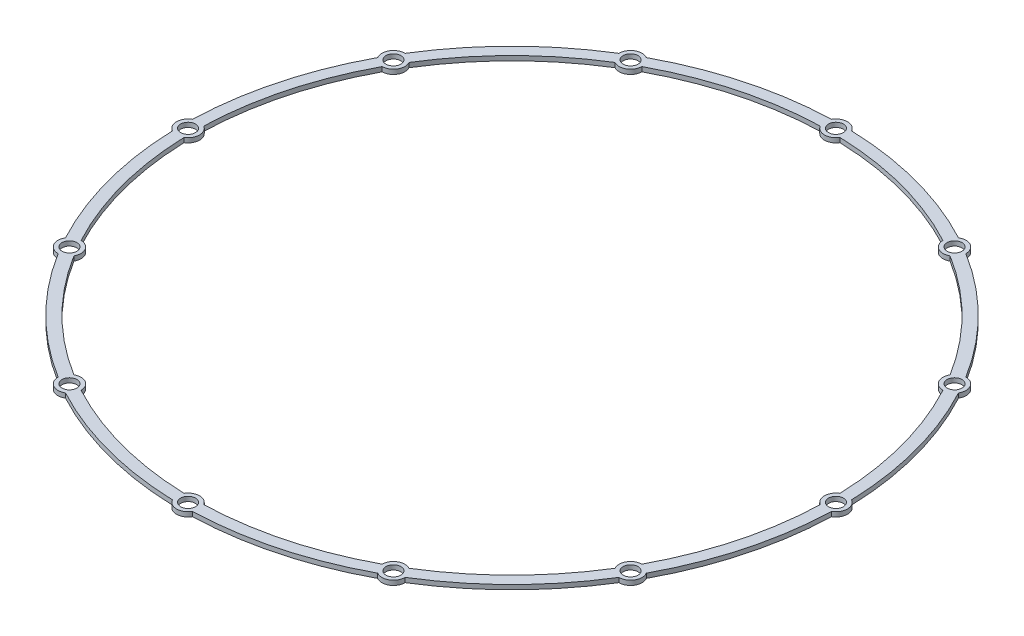
SolidWorks part; units mm, degrees
material "6061 Alloy"
ref_plane "Front Plane" through (0, 0, 0) normal (0, 0, 1) x (1, 0, 0)
ref_plane "Top Plane" through (0, 0, 0) normal (0, 1, 0) x (1, 0, 0)
ref_plane "Right Plane" through (0, 0, 0) normal (1, 0, 0) x (0, 0, -1)
sketch "Sketch1" plane through (0, 0, 0) normal (0, 1, 0) x (1, 0, 0)
  circle A0 centre (0, 0) radius 71.755 construction
  circle A1 centre (0, 0) radius 73.025
  circle A2 centre (0, 0) radius 70.485
  circle A3 centre (0, 0) radius 74.295
  circle A4 centre (0, 0) radius 69.215
  circle A5 centre (0, -71.755) radius 1.651
  circle A6 centre (0, -71.755) radius 2.54
  dimension "D1" = 143.51
  dimension "D6" = 3.302
  dimension "D2" = 1.27
  dimension "D3" = 1.27
  dimension "D4" = 2.54
  dimension "D5" = 2.54
extrude "Boss-Extrude1" add sketch "Sketch1" along normal blind 1.016 contours A6 A1 A2 | A2 A6 A1 A5 | A1 A5 A2 | A1 A6 A2 A5 region at (50.9327, 0, 49.408) region at (-1.9394, 0, 71.7321) region at (1.9394, 0, 71.7321) region at (0, 0, 71.7531)
extrude "Boss-Extrude2" add sketch "Sketch1<3>" along normal blind 1.016 contours A2 A6 A5 | A6 A1 A5 region at (0, 0, 73.5973) region at (0, 0, 69.8977)
sketch "Sketch1<3>" plane through (0, 0, 0) normal (0, 1, 0) x (1, 0, 0) same geometry as "Sketch1"
extrude "Cut-Extrude1" cut sketch "Sketch1<4>" along normal up to surface (1.016 mm away) contours A1 A5 | A2 A5 | A1 A5 A2 region at (0, 0, 71.7531) region at (0, 0, 73.1775) region at (0, 0, 70.3295) up to face at (0, 1.016, 0.635)
sketch "Sketch1<4>" plane through (0, 0, 0) normal (0, 1, 0) x (1, 0, 0) same geometry as "Sketch1"
pattern_circular "CirPattern2" count 12 over 360 about axis through (0, 1.016, 0) along (0, 1, 0) of "Cut-Extrude1", "Boss-Extrude2"
ref_plane "Plane1" through (0, 0.508, 0) normal (0, 1, 0) x (1, 0, 0)
sketch "Sketch2" plane through (0, 0.508, 0) normal (0, 1, 0) x (1, 0, 0)
  circle A0 centre (-62.1417, 35.8775) radius 1.651 construction
  circle A1 centre (-35.8775, 62.1417) radius 1.651 construction
  circle A2 centre (-71.755, 0) radius 1.651 construction
  circle A3 centre (-62.1417, -35.8775) radius 1.651 construction
  circle A4 centre (-35.8775, -62.1417) radius 1.651 construction
  circle A5 centre (0, -71.755) radius 1.651 construction
  circle A6 centre (35.8775, -62.1417) radius 1.651 construction
  circle A7 centre (62.1417, -35.8775) radius 1.651 construction
  circle A8 centre (71.755, 0) radius 1.651 construction
  circle A9 centre (62.1417, 35.8775) radius 1.651 construction
  circle A10 centre (35.8775, 62.1417) radius 1.651 construction
  circle A11 centre (0, 71.755) radius 1.651 construction
  circle A12 centre (-62.1417, 35.8775) radius 1.651
  circle A13 centre (-71.755, 0) radius 1.651
  circle A14 centre (-62.1417, -35.8775) radius 1.651
  circle A15 centre (-35.8775, -62.1417) radius 1.651
  circle A16 centre (0, -71.755) radius 1.651
  circle A17 centre (35.8775, -62.1417) radius 1.651
  circle A18 centre (62.1417, -35.8775) radius 1.651
  circle A19 centre (71.755, 0) radius 1.651
  circle A20 centre (62.1417, 35.8775) radius 1.651
  circle A21 centre (35.8775, 62.1417) radius 1.651
  circle A22 centre (0, 71.755) radius 1.651
  circle A23 centre (-35.8775, 62.1417) radius 1.651
  arc A24 (-38.4172, -62.1029) -> (-34.5741, -64.3217) centre (-35.8775, -62.1417) ccw
  arc A25 (-34.5741, -64.3217) -> (-2.2188, -72.9913) centre (0, 0) ccw
  arc A26 (-2.2188, -72.9913) -> (2.2188, -72.9913) centre (0, -71.755) ccw
  arc A27 (2.2188, -72.9913) -> (34.5741, -64.3217) centre (0, 0) ccw
  arc A28 (34.5741, -64.3217) -> (38.4172, -62.1029) centre (35.8775, -62.1417) ccw
  arc A29 (38.4172, -62.1029) -> (62.1029, -38.4172) centre (0, 0) ccw
  arc A30 (62.1029, -38.4172) -> (64.3217, -34.5741) centre (62.1417, -35.8775) ccw
  arc A31 (64.3217, -34.5741) -> (72.9913, -2.2188) centre (0, 0) ccw
  arc A32 (72.9913, -2.2188) -> (72.9913, 2.2188) centre (71.755, 0) ccw
  arc A33 (72.9913, 2.2188) -> (64.3217, 34.5741) centre (0, 0) ccw
  arc A34 (64.3217, 34.5741) -> (62.1029, 38.4172) centre (62.1417, 35.8775) ccw
  arc A35 (62.1029, 38.4172) -> (38.4172, 62.1029) centre (0, 0) ccw
  arc A36 (38.4172, 62.1029) -> (34.5741, 64.3217) centre (35.8775, 62.1417) ccw
  arc A37 (34.5741, 64.3217) -> (2.2188, 72.9913) centre (0, 0) ccw
  arc A38 (2.2188, 72.9913) -> (-2.2188, 72.9913) centre (0, 71.755) ccw
  arc A39 (-2.2188, 72.9913) -> (-34.5741, 64.3217) centre (0, 0) ccw
  arc A40 (-34.5741, 64.3217) -> (-38.4172, 62.1029) centre (-35.8775, 62.1417) ccw
  arc A41 (-38.4172, 62.1029) -> (-62.1029, 38.4172) centre (0, 0) ccw
  arc A42 (-62.1029, 38.4172) -> (-64.3217, 34.5741) centre (-62.1417, 35.8775) ccw
  arc A43 (-64.3217, 34.5741) -> (-72.9913, 2.2188) centre (0, 0) ccw
  arc A44 (-72.9913, 2.2188) -> (-72.9913, -2.2188) centre (-71.755, 0) ccw
  arc A45 (-72.9913, -2.2188) -> (-64.3217, -34.5741) centre (0, 0) ccw
  arc A46 (-64.3217, -34.5741) -> (-62.1029, -38.4172) centre (-62.1417, -35.8775) ccw
  arc A47 (-62.1029, -38.4172) -> (-38.4172, -62.1029) centre (0, 0) ccw
  arc A48 (-38.4172, -62.1029) -> (-34.5741, -64.3217) centre (-35.8775, -62.1417) ccw
  arc A49 (-34.5741, -64.3217) -> (-2.2188, -72.9913) centre (0, 0) ccw
  arc A50 (-2.2188, -72.9913) -> (2.2188, -72.9913) centre (0, -71.755) ccw
  arc A51 (2.2188, -72.9913) -> (34.5741, -64.3217) centre (0, 0) ccw
  arc A52 (34.5741, -64.3217) -> (38.4172, -62.1029) centre (35.8775, -62.1417) ccw
  arc A53 (38.4172, -62.1029) -> (62.1029, -38.4172) centre (0, 0) ccw
  arc A54 (62.1029, -38.4172) -> (64.3217, -34.5741) centre (62.1417, -35.8775) ccw
  arc A55 (64.3217, -34.5741) -> (72.9913, -2.2188) centre (0, 0) ccw
  arc A56 (72.9913, -2.2188) -> (72.9913, 2.2188) centre (71.755, 0) ccw
  arc A57 (72.9913, 2.2188) -> (64.3217, 34.5741) centre (0, 0) ccw
  arc A58 (64.3217, 34.5741) -> (62.1029, 38.4172) centre (62.1417, 35.8775) ccw
  arc A59 (62.1029, 38.4172) -> (38.4172, 62.1029) centre (0, 0) ccw
  arc A60 (38.4172, 62.1029) -> (34.5741, 64.3217) centre (35.8775, 62.1417) ccw
  arc A61 (34.5741, 64.3217) -> (2.2188, 72.9913) centre (0, 0) ccw
  arc A62 (2.2188, 72.9913) -> (-2.2188, 72.9913) centre (0, 71.755) ccw
  arc A63 (-2.2188, 72.9913) -> (-34.5741, 64.3217) centre (0, 0) ccw
  arc A64 (-34.5741, 64.3217) -> (-38.4172, 62.1029) centre (-35.8775, 62.1417) ccw
  arc A65 (-38.4172, 62.1029) -> (-62.1029, 38.4172) centre (0, 0) ccw
  arc A66 (-62.1029, 38.4172) -> (-64.3217, 34.5741) centre (-62.1417, 35.8775) ccw
  arc A67 (-64.3217, 34.5741) -> (-72.9913, 2.2188) centre (0, 0) ccw
  arc A68 (-72.9913, 2.2188) -> (-72.9913, -2.2188) centre (-71.755, 0) ccw
  arc A69 (-72.9913, -2.2188) -> (-64.3217, -34.5741) centre (0, 0) ccw
  arc A70 (-64.3217, -34.5741) -> (-62.1029, -38.4172) centre (-62.1417, -35.8775) ccw
  arc A71 (-62.1029, -38.4172) -> (-38.4172, -62.1029) centre (0, 0) ccw
  dimension "D1" = 0
equation "\"Middle Coupler Inner Daimeter\"= 4.75in"
equation "\"Middle Coupler  Wall Thickness\" = 0.25in"
equation "\"Middle Coupler Bottom Thickness\"= 0.2in"
equation "\"Bearing Rail Offset\"= 0.45in"
equation "\"3-56 UNF Tap\"= 0.089in"
equation "\"3-56 UNF Clearance\"= 0.104in"
equation "\"Ball Bearing Distance\"= 0.03in"
equation "\"TCA Outer Diameter\" = 6.625in"
equation "\"D1@Sketch1\"=\"Middle Coupler Inner Daimeter\"+\"Bearing Rail Offset\"*2in"
equation "\"Interstage Aeroframe Wall Thickness\" = 0.072in"
equation "\"Compression Spring OD\"= 0.42in"
equation "\"10-24 Tap\"= 0.157in"
equation "\"10-24 Clearance\"= 0.196in"
equation "\"Lower Stage Fuselage Wall Thickness\" = 0.25in"
equation "\"6-32 Tap\" = 0.107in"
equation "\"1/4-20 Tap\" = 0.201in"
